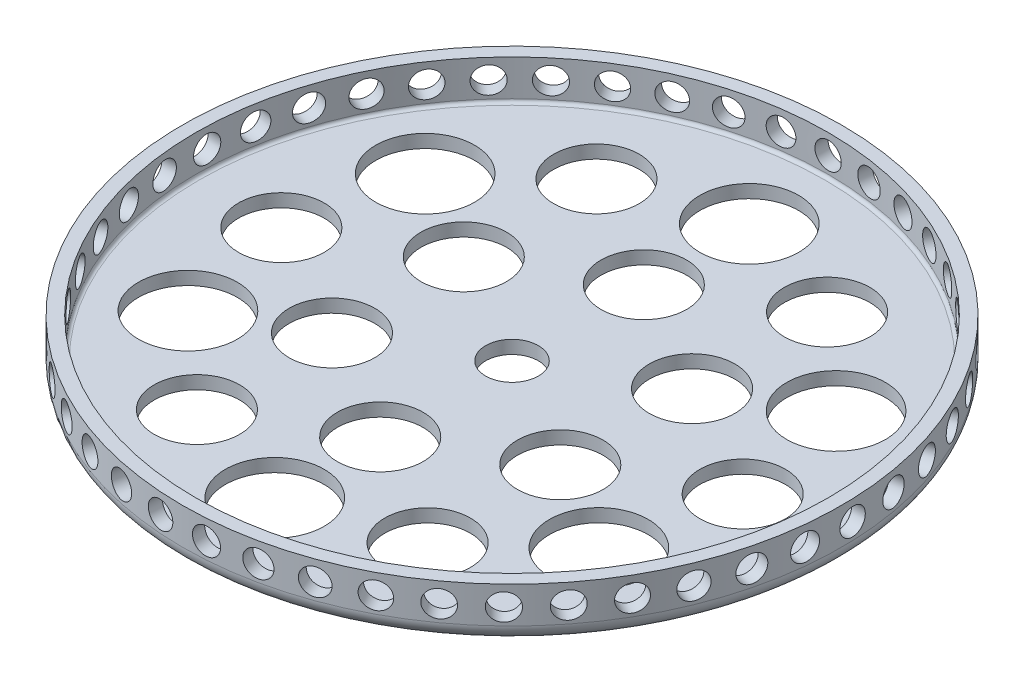
SolidWorks part; units mm, degrees
material "1060 Alloy"
ref_plane "Front Plane" through (0, 0, 0) normal (0, 0, 1) x (1, 0, 0)
ref_plane "Top Plane" through (0, 0, 0) normal (0, 1, 0) x (1, 0, 0)
ref_plane "Right Plane" through (0, 0, 0) normal (1, 0, 0) x (0, 0, -1)
sketch "Sketch5" plane through (0, 0, 0) normal (0, 1, 0) x (1, 0, 0)
  circle A0 centre (0, 0) radius 33.02
  dimension "D1" = 66.04
sketch "Dimmension" plane through (0, 0, 0) normal (0, 1, 0) x (1, 0, 0)
  circle A0 centre (0, 0) radius 31.75
  dimension "D1" = 63.5
extrude "Overall Plate Size" add sketch "Dimmension" along normal blind 5.08
fillet "Fillet3" radius 1.5875 1 edges at (0, 0, 31.75)
shell "Shell1" thickness 1.27 removed face at (0, 5.08, 31.75)
sketch "Dimmensions" plane through (0, 1.27, 0) normal (0, 1, 0) x (1, 0, 0)
  line L0 (0, 30.1625) -> (0, 0) construction
  line L1 (0, 0) -> (30.1625, 0) construction
  circle A0 centre (0, 0) radius 30.1625 construction
  circle A1 centre (0, 22.86) radius 4.7625
  circle A2 centre (0, 12.7) radius 4.1275
  circle A3 centre (19.7973, 11.43) radius 4.7625
  circle A4 centre (10.9985, 6.35) radius 4.1275
  circle A5 centre (19.7973, -11.43) radius 4.7625
  circle A6 centre (10.9985, -6.35) radius 4.1275
  circle A7 centre (0, -22.86) radius 4.7625
  circle A8 centre (0, -12.7) radius 4.1275
  circle A9 centre (-19.7973, -11.43) radius 4.7625
  circle A10 centre (-10.9985, -6.35) radius 4.1275
  circle A11 centre (-19.7973, 11.43) radius 4.7625
  circle A12 centre (-10.9985, 6.35) radius 4.1275
  circle A13 centre (22.225, 0) radius 4.1275
  circle A14 centre (11.1125, -19.2474) radius 4.1275
  circle A15 centre (-11.1125, -19.2474) radius 4.1275
  circle A16 centre (-22.225, 0) radius 4.1275
  circle A17 centre (-11.1125, 19.2474) radius 4.1275
  circle A18 centre (11.1125, 19.2474) radius 4.1275
  circle A19 centre (0, 0) radius 2.54
  point P32 (0, 0)
  point P45 (0, 0)
  dimension "D2" = 9.525
  dimension "D3" = 8.255
  dimension "D5" = 8.255
  dimension "D7" = 5.08
  dimension "D1" = 22.86
  dimension "D4" = 12.7
  dimension "D6" = 22.225
extrude "Y holes" cut sketch "Dimmensions" against normal up to next
sketch "Sketch4" plane through (0, 0, 0) normal (0, 0, 1) x (1, 0, 0)
  line L0 (0, 0) -> (0, 5.08) construction
  line L1 (-30.1625, 0) -> (30.1625, 0) construction
  line L2 (30.48, 5.08) -> (-30.48, 5.08) construction
  circle A0 centre (0, 3.175) radius 1.27
  dimension "D2" = 2.54
  dimension "D1" = 3.175
extrude "Spring holes" cut sketch "Sketch4" against normal through all
pattern_circular "CirPattern1" count 45 over 360 about axis through (0, 1.27, 0) along (0, 1, 0) of "Spring holes"
